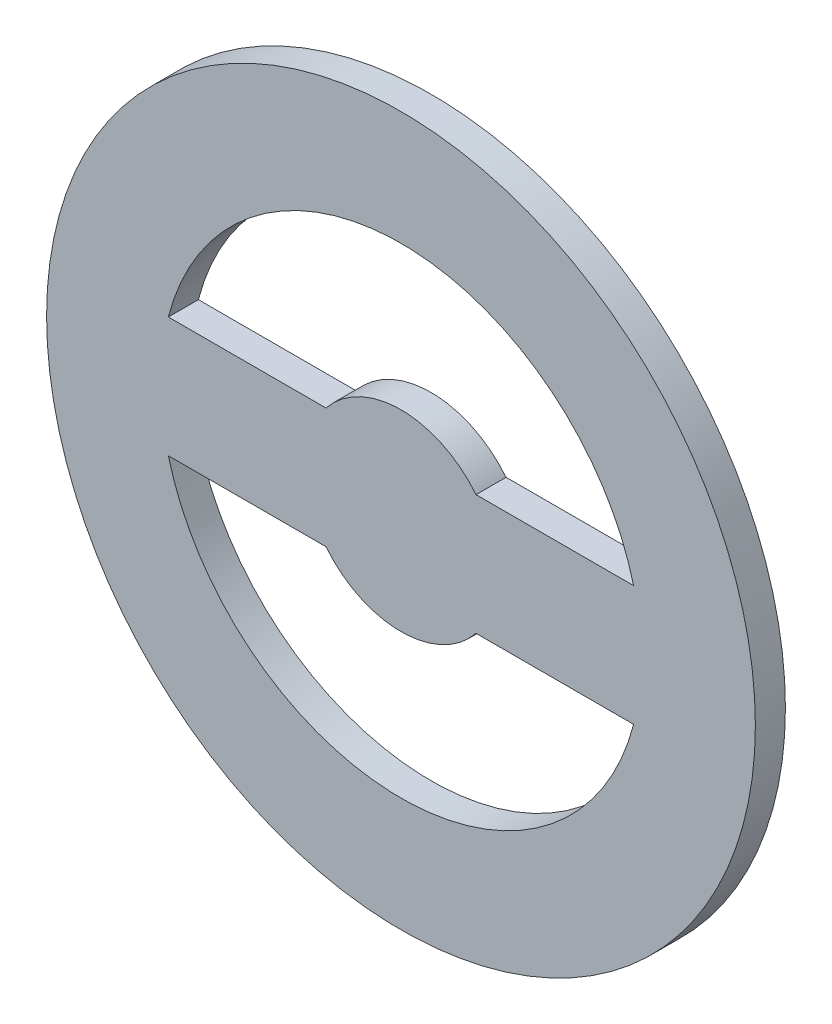
SolidWorks part; units mm, degrees
ref_plane "Front Plane" through (0, 0, 0) normal (0, 0, 1) x (1, 0, 0)
ref_plane "Top Plane" through (0, 0, 0) normal (0, 1, 0) x (1, 0, 0)
ref_plane "Right Plane" through (0, 0, 0) normal (1, 0, 0) x (0, 0, -1)
sketch "Sketch1" plane through (0, 0, 0) normal (0, 0, 1) x (1, 0, 0)
  circle A0 centre (0, 0) radius 37.465
  dimension "D1" = 74.93
extrude "Boss-Extrude1" add sketch "Sketch1" along normal blind 3.175
sketch "Sketch2" plane through (0, 0, 3.175) normal (0, 0, 1) x (1, 0, 0)
  line L0 (-24.5934, -6.35) -> (-7.9311, -6.35)
  line L1 (7.9311, 6.35) -> (24.5934, 6.35)
  line L2 (7.9311, -6.35) -> (24.5934, -6.35)
  line L3 (-24.5934, 6.35) -> (-7.9311, 6.35)
  line L4 (-24.5934, -6.35) -> (24.5934, 6.35) construction
  line L5 (24.5934, -6.35) -> (-24.5934, 6.35) construction
  arc A0 (7.9311, 6.35) -> (-7.9311, 6.35) centre (0, 0) ccw
  arc A1 (-24.5934, -6.35) -> (24.5934, -6.35) centre (0, 0) ccw
  arc A2 (24.5934, 6.35) -> (-24.5934, 6.35) centre (0, 0) ccw
  arc A3 (-7.9311, -6.35) -> (7.9311, -6.35) centre (0, 0) ccw
  dimension "D1" = 20.32
  dimension "D2" = 50.8
  dimension "D3" = 12.7
extrude "Cut-Extrude1" cut sketch "Sketch2" against normal through all
